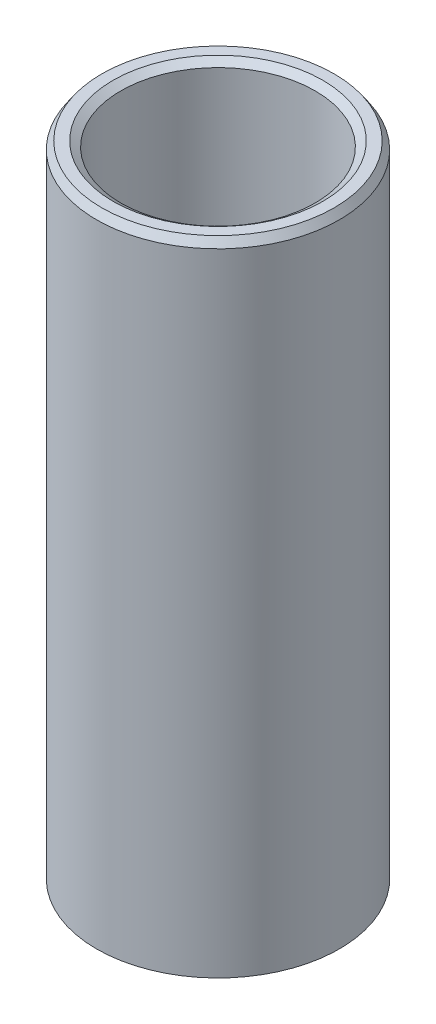
SolidWorks part; units mm, degrees
ref_plane "Front Plane" through (0, 0, 0) normal (0, 0, 1) x (1, 0, 0)
ref_plane "Top Plane" through (0, 0, 0) normal (0, 1, 0) x (1, 0, 0)
ref_plane "Right Plane" through (0, 0, 0) normal (1, 0, 0) x (0, 0, -1)
sketch "Sketch1" plane through (0, 0, 0) normal (0, 1, 0) x (1, 0, 0)
  circle A0 centre (0, 0) radius 55
  dimension "SLEEVE_OD" = 110
extrude "Boss-Extrude1" add sketch "Sketch1" along normal blind 291.9329
sketch "Sketch2" plane through (0, 0, 0) normal (0, 1, 0) x (1, 0, 0)
  circle A0 centre (0, 0) radius 44.0274
  dimension "BORE_D" = 88.0548
extrude "Cut-Extrude1" cut sketch "Sketch2" along normal through all
chamfer "Chamfer1" distance 3.4939 angle 34.412 4 edges at (0, 291.9329, 44.0274) (0, 0, 44.0274) (0, 0, 55) (0, 291.9329, 55) first distance on face at (0, 291.9329, 44.0274) first distance on face at (0, 0, 44.0274) first distance on face at (0, 291.9329, 55)
